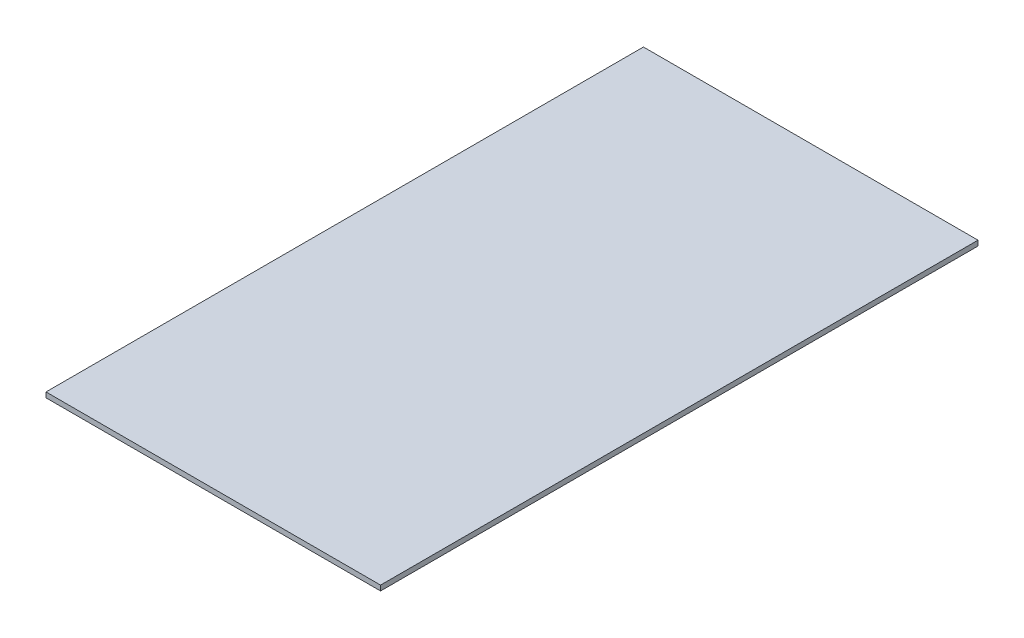
SolidWorks part; units mm, degrees
ref_plane "Front Plane" through (0, 0, 0) normal (0, 0, 1) x (1, 0, 0)
ref_plane "Top Plane" through (0, 0, 0) normal (0, 1, 0) x (1, 0, 0)
ref_plane "Right Plane" through (0, 0, 0) normal (1, 0, 0) x (0, 0, -1)
sketch "Sketch1" plane through (0, 0, 0) normal (0, 1, 0) x (1, 0, 0)
  line L1 (0, 0) -> (196, 0)
  line L2 (0, 0) -> (0, 350)
  line L3 (0, 350) -> (196, 350)
  line L4 (196, 0) -> (196, 350)
  dimension "D1" = 350
  dimension "D2" = 196
extrude "Boss-Extrude1" add sketch "Sketch1" along normal blind 3
